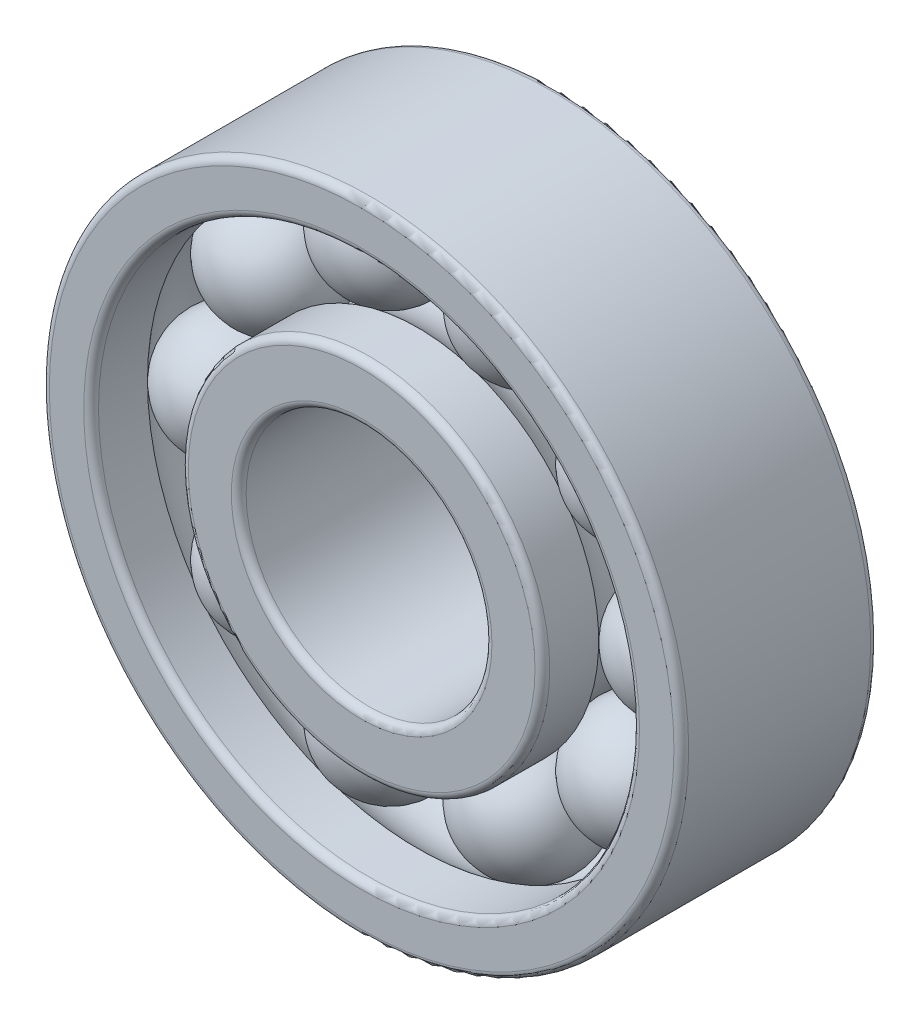
SolidWorks part; units mm, degrees
ref_plane "Front Plane" through (0, 0, 0) normal (0, 0, 1) x (1, 0, 0)
ref_plane "Top Plane" through (0, 0, 0) normal (0, 1, 0) x (1, 0, 0)
ref_plane "Right Plane" through (0, 0, 0) normal (1, 0, 0) x (0, 0, -1)
sketch "Sketch1" plane through (0, 0, 0) normal (0, 0, 1) x (1, 0, 0)
  circle A0 centre (0, 0) radius 13
  circle A1 centre (0, 0) radius 5
  circle A2 centre (0, 0) radius 7.35
  circle A3 centre (0, 0) radius 11
  dimension "D1" = 26
  dimension "D2" = 10
  dimension "D3" = 14.7
  dimension "D4" = 22
extrude "Boss-Extrude1" add sketch "Sketch1" along normal blind 8 contours A0 | A3 | A2 | A1
ref_plane "Middle Plane" through (0, 0, 4) normal (0, 0, 1) x (1, 0, 0)
sketch "Sketch2" plane through (0, 0, 4) normal (0, 0, 1) x (1, 0, 0)
  circle A0 centre (0, 0) radius 9.175
  dimension "D1" = 18.35
sketch "Sketch3" plane through (0, 0, 0) normal (0, 1, 0) x (1, 0, 0)
  line L0 (0, 0) -> (0, -8) construction
  line L1 (-13, -8) -> (13, -8) construction
ref_axis "Axis1" through (0, 0, 0) along (0, 0, 1)
sketch "Sketch4" plane through (0, 0, 0) normal (0, 1, 0) x (1, 0, 0)
  line L0 (0, 0) -> (0, -8) construction
  line L1 (-13, -4) -> (13, -4) construction
  line L2 (-13, 0) -> (-13, -8) construction
  line L3 (13, -8) -> (13, 0) construction
  circle A0 centre (-9.175, -4) radius 2.5
  point P10 (0, -4)
  dimension "D2" = 5
  dimension "D1" = 9.175
sweep "Cut-Sweep1" cut profiles "Sketch4" path "Sketch2"
sketch "Sketch5" plane through (0, 0, 0) normal (0, 1, 0) x (1, 0, 0)
  line L0 (0, 0) -> (0, -8) construction
  line L1 (-13, -4) -> (13, -4) construction
  line L2 (-13, 0) -> (-13, -8) construction
  line L3 (13, -8) -> (13, 0) construction
  line L4 (-9.175, -1.5) -> (-9.175, -6.5)
  arc A0 (-9.175, -1.5) -> (-9.175, -6.5) centre (-9.175, -4) ccw
  point P10 (0, -4)
  dimension "D1" = 2.5
  dimension "D2" = 9.175
revolve "Revolve1" add sketch "Sketch5" angle 360 about L4
pattern_circular "CirPattern1" count 10 over 360 about axis through (0, 0, 8) along (0, 0, -1) reverse direction yes of bodies 105
fillet "Fillet1" radius 0.3 4 edges at (11, 0, 0) (13, 0, 0) (11, 0, 8) (13, 0, 8)
fillet "Fillet2" radius 0.3 4 edges at (5, 0, 8) (7.35, 0, 8) (5, 0, 0) (7.35, 0, 0)
